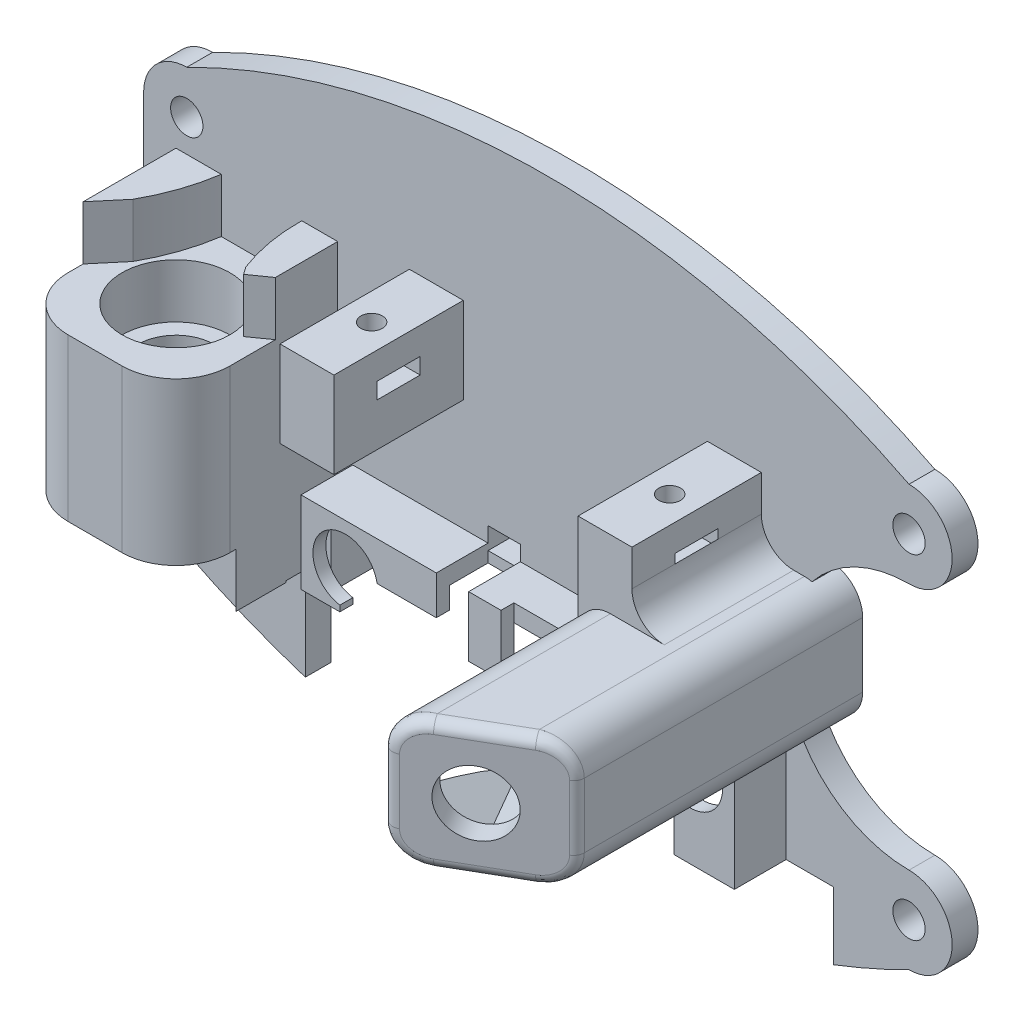
SolidWorks part; units mm, degrees
material "ABS"
ref_plane "Alzado" through (0, 0, 0) normal (0, 0, 1) x (1, 0, 0)
ref_plane "Planta" through (0, 0, 0) normal (0, 1, 0) x (1, 0, 0)
ref_plane "Vista lateral" through (0, 0, 0) normal (1, 0, 0) x (0, 0, -1)
sketch "Croquis1" plane through (0, 0, 0) normal (0, 0, 1) x (1, 0, 0)
  line L0 (-65.9407, 48.6885) -> (-65.9407, 17.6885)
  line L1 (-61.9407, 52.6885) -> (5.0593, 52.6885) construction
  line L2 (-61.9407, 13.6885) -> (5.0593, 13.6885) construction
  line L3 (-28.4407, 52.6885) -> (-28.4407, 60.6885) construction
  line L4 (-28.4407, 13.6885) -> (-28.4407, 5.6885) construction
  circle A0 centre (-61.9407, 48.6885) radius 1.5
  circle A1 centre (5.0593, 48.6885) radius 1.5
  circle A2 centre (5.0593, 17.6885) radius 1.5
  circle A3 centre (-61.9407, 17.6885) radius 1.5
  arc A4 (-61.9407, 52.6885) -> (-65.9407, 48.6885) centre (-61.9407, 48.6885) ccw
  arc A5 (-65.9407, 17.6885) -> (-61.9407, 13.6885) centre (-61.9407, 17.6885) ccw
  arc A6 (-61.9407, 13.6885) -> (5.0593, 13.6885) centre (-28.4407, 79.8291) ccw
  arc A7 (5.0593, 13.6885) -> (5.0593, 21.6885) centre (5.0593, 17.6885) ccw
  arc A8 (5.0593, 44.6885) -> (5.0593, 21.6885) centre (5.0593, 33.1885) ccw
  arc A9 (5.0593, 44.6885) -> (5.0593, 52.6885) centre (5.0593, 48.6885) ccw
  arc A10 (5.0593, 52.6885) -> (-61.9407, 52.6885) centre (-28.4407, -13.4521) ccw
  dimension "D2" = 8
  dimension "D3" = 8
  dimension "D5" = 4
  dimension "D6" = 4
  dimension "D7" = 3
  dimension "D8" = 3
  dimension "D9" = 4
  dimension "D10" = 3
  dimension "D11" = 4
  dimension "D12" = 3
  dimension "D13" = 11.5
  dimension "D1" = 67
  dimension "D4" = 31
extrude "Saliente-Extruir1" add sketch "Croquis1" along normal blind 2.4
sketch "Croquis3" plane through (0, 0, 2.4) normal (0, 0, 1) x (1, 0, 0)
  line L1 (-36.2907, 53.2855) -> (-13.6407, 53.2855)
  line L2 (-36.2907, 53.2855) -> (-36.2907, 49.2855)
  line L3 (-36.2907, 31.0355) -> (-13.6407, 31.0355)
  line L4 (-13.6407, 53.2855) -> (-13.6407, 49.2855)
  line L8 (-51.8407, 27.8355) -> (-51.8407, 7.4355) construction
  line L9 (-50.6407, 26.6355) -> (-13.6407, 26.6355) construction
  line L10 (-50.6407, 26.6355) -> (-50.6407, 8.6355) construction
  line L11 (-50.6407, 8.6355) -> (-13.6407, 8.6355) construction
  line L12 (-13.6407, 26.6355) -> (-13.6407, 8.6355) construction
  line L13 (-51.8407, 7.4355) -> (-12.4407, 7.4355) construction
  line L14 (-12.4407, 27.8355) -> (-12.4407, 7.4355) construction
  line L15 (-51.8407, 27.8355) -> (-12.4407, 27.8355) construction
  line L16 (-6.4407, 33.1885) -> (-12.4407, 33.1885) construction
  line L17 (-13.6407, 49.2855) -> (-8.6407, 49.2855)
  line L18 (-8.6407, 49.2855) -> (-8.6407, 46.7855)
  line L19 (-8.6407, 46.7855) -> (-13.6407, 46.7855)
  line L20 (-13.6407, 46.7855) -> (-13.6407, 31.0355)
  line L21 (-24.9657, 31.0355) -> (-24.9657, 53.2855) construction
  line L22 (-36.2907, 49.2855) -> (-41.2907, 49.2855)
  line L23 (-41.2907, 49.2855) -> (-41.2907, 46.7855)
  line L24 (-41.2907, 46.7855) -> (-36.2907, 46.7855)
  line L25 (-36.2907, 46.7855) -> (-36.2907, 31.0355)
  arc A0 (5.0593, 44.6885) -> (5.0593, 21.6885) centre (5.0593, 33.1885) ccw construction
  arc A1 (-61.9407, 13.6885) -> (5.0593, 13.6885) centre (-28.4407, 79.8291) ccw construction
  point P31 (-9.4407, 33.1885)
  dimension "D1" = 22.65
  dimension "D2" = 22.25
  dimension "D4" = 18
  dimension "D5" = 37
  dimension "D7" = 6
  dimension "D8" = 5
  dimension "D3" = 4
  dimension "D9" = 2.5
  dimension "D10" = 2.153
  dimension "D6" = 1.2
sketch "Croquis8" plane through (0, 0, 2.4) normal (0, 0, 1) x (1, 0, 0)
  line L0 (-6.4407, 33.1885) -> (-65.9407, 33.1885) construction
  line L1 (-65.9407, 48.6885) -> (-65.9407, 17.6885) construction
  line L3 (-62.9407, 40.6885) -> (-47.9407, 40.6885)
  line L4 (-62.9407, 40.6885) -> (-62.9407, 25.6885)
  line L5 (-62.9407, 25.6885) -> (-47.9407, 25.6885)
  line L6 (-47.9407, 40.6885) -> (-47.9407, 25.6885)
  arc A0 (5.0593, 44.6885) -> (5.0593, 21.6885) centre (5.0593, 33.1885) ccw construction
  point P11 (-47.9407, 33.1885)
  dimension "D1" = 15
  dimension "D2" = 15
  dimension "D3" = 3
extrude "Saliente-Extruir5" add sketch "Croquis8" along normal blind 15
sketch "Croquis10" plane through (0, 25.6885, 0) normal (0, -1, 0) x (1, 0, 0)
  line L0 (-62.9407, 2.4) -> (-47.9407, 2.4) construction
  line L1 (-62.9407, 17.4) -> (-47.9407, 17.4) construction
  circle A0 centre (-55.4407, 9.9) radius 5
  point P7 (-55.4407, 17.4)
  dimension "D1" = 10
  dimension "D2" = 7.5
extrude "Cortar-Extruir2" cut sketch "Croquis10" against normal blind 5
extrude "Cortar-Extruir3" cut sketch "Croquis10<2>" along normal blind 5 from surface starting at face at (-55.4407, 40.6885, 9.9)
sketch "Croquis10<2>" plane through (0, 25.6885, 0) normal (0, -1, 0) x (1, 0, 0) same geometry as "Croquis10"
sketch "Croquis11" plane through (0, 30.6885, 0) normal (0, -1, 0) x (1, 0, 0)
  circle A0 centre (-55.4407, 9.9) radius 3.5
  dimension "D1" = 7
extrude "Cortar-Extruir4" cut sketch "Croquis11" against normal up to surface (5 mm away) up to face at (-50.4407, 35.6885, 9.9)
fillet "Redondeo1" radius 5 2 edges at (-47.9407, 33.1885, 17.4) (-62.9407, 33.1885, 17.4)
sketch "Croquis14" plane through (0, 0, 2.4) normal (0, 0, 1) x (1, 0, 0)
  line L1 (-44.9407, 26.8355) -> (-7.9407, 26.8355)
  line L2 (-44.9407, 26.8355) -> (-44.9407, 1.8355)
  line L3 (-44.9407, 1.8355) -> (-7.9407, 1.8355)
  line L4 (-7.9407, 26.8355) -> (-7.9407, 1.8355)
  line L5 (-47.9407, 25.6885) -> (-47.9407, 40.6885) construction
  line L6 (-24.9657, 29.8355) -> (-24.9657, 26.8355) construction
  line L7 (-33.9907, 29.8355) -> (-30.9907, 29.8355)
  line L8 (-33.9907, 29.8355) -> (-33.9907, 27.8355)
  line L9 (-33.9907, 27.8355) -> (-30.9907, 27.8355)
  line L10 (-30.9907, 29.8355) -> (-30.9907, 27.8355)
  line L11 (-47.9407, 40.6885) -> (-62.9407, 40.6885) construction
  dimension "D1" = 37
  dimension "D2" = 25
  dimension "D3" = 1
  dimension "D4" = 3
  dimension "D5" = 2
  dimension "D6" = 3
  dimension "D7" = 13.95
  dimension "D8" = 13.853
extrude "Cortar-Extruir7" cut sketch "Croquis14" against normal up to next
sketch "Croquis15" plane through (0, 0, 2.4) normal (0, 0, 1) x (1, 0, 0)
  line L0 (-44.9407, 7.5479) -> (-44.9407, 26.8355)
  line L1 (-44.9407, 26.8355) -> (-33.9907, 26.8355)
  line L2 (-7.9407, 26.8355) -> (-7.9407, 8.579)
  line L3 (-46.5407, 7.9318) -> (-46.5407, 28.4355)
  line L4 (-46.5407, 28.4355) -> (-33.9907, 28.4355)
  line L5 (-33.9907, 29.8355) -> (-33.9907, 27.8355) construction
  line L6 (-33.9907, 28.4355) -> (-33.9907, 26.8355)
  line L7 (-30.9907, 28.4355) -> (-30.9907, 26.8355)
  line L8 (-30.9907, 27.8355) -> (-30.9907, 29.8355) construction
  line L9 (-30.9907, 26.8355) -> (-7.9407, 26.8355)
  line L10 (-30.9907, 28.4355) -> (-6.3407, 28.4355)
  line L11 (-6.3407, 28.4355) -> (-6.3407, 9.0589)
  arc A0 (-61.9407, 13.6885) -> (-44.9407, 7.5479) centre (-28.4407, 79.8291) ccw construction
  arc A1 (-7.9407, 8.579) -> (5.0593, 13.6885) centre (-28.4407, 79.8291) ccw construction
  arc A9 (-61.9407, 13.6885) -> (-44.9407, 7.5479) centre (-28.4407, 79.8291) ccw
  arc A10 (-46.5407, 7.9318) -> (-44.9407, 7.5479) centre (-28.4407, 79.8291) ccw
  arc A12 (-7.9407, 8.579) -> (5.0593, 13.6885) centre (-28.4407, 79.8291) ccw
  arc A13 (-7.9407, 8.579) -> (-6.3407, 9.0589) centre (-28.4407, 79.8291) ccw
  dimension "D1" = 1.6
  dimension "D2" = 1.6
  dimension "D3" = 1.6
  dimension "D4" = 1.6
  dimension "D5" = 0
  dimension "D6" = 0
extrude "Saliente-Extruir6" add sketch "Croquis15" along normal blind 3.6
sketch "Croquis16" plane through (0, 0, 6) normal (0, 0, 1) x (1, 0, 0)
  line L0 (-33.9907, 28.4355) -> (-46.5407, 28.4355)
  line L3 (-46.5407, 28.4355) -> (-46.5407, 7.9318)
  line L4 (-30.9907, 28.4355) -> (-6.3407, 28.4355)
  line L5 (-6.3407, 28.4355) -> (-6.3407, 9.0589)
  line L11 (-42.9407, 24.8355) -> (-33.9907, 24.8355)
  line L12 (-42.9407, 7.5479) -> (-42.9407, 24.8355)
  line L13 (-42.9407, 24.8355) -> (-33.9907, 24.8355)
  line L14 (-42.9407, 7.1202) -> (-42.9407, 24.8355)
  line L16 (-33.9907, 28.4355) -> (-33.9907, 24.8355)
  line L17 (-30.9907, 28.4355) -> (-30.9907, 22.8355)
  line L18 (-11.9407, 22.8355) -> (-11.9407, 8.579)
  line L19 (-30.9907, 22.8355) -> (-11.9407, 22.8355)
  line L20 (-11.9407, 22.8355) -> (-11.9407, 7.5479)
  line L21 (-30.9907, 22.8355) -> (-11.9407, 22.8355)
  arc A0 (-46.5407, 7.9318) -> (-42.9407, 7.1202) centre (-28.4407, 79.8291) ccw
  arc A1 (-11.9407, 7.5479) -> (-6.3407, 9.0589) centre (-28.4407, 79.8291) ccw
  dimension "D1" = 2
  dimension "D2" = 4
extrude "Saliente-Extruir7" add sketch "Croquis16" along normal blind 1.2
sketch "Croquis20" plane through (0, 25.6885, 0) normal (0, -1, 0) x (1, 0, 0)
  line L0 (-62.9407, 2.4) -> (-62.9407, 11.012)
  line L1 (-62.9407, 12.4) -> (-62.9407, 2.4) construction
  line L2 (-62.9407, 11.012) -> (-60.8397, 8.5116)
  line L4 (-62.9407, 2.4) -> (-47.9407, 2.4) construction
  line L5 (-58.7388, 2.4) -> (-62.9407, 2.4)
  line L6 (-47.9407, 2.4) -> (-47.9407, 11.8496)
  line L7 (-47.9407, 12.4) -> (-47.9407, 2.4) construction
  line L10 (-51.275, 2.4) -> (-47.9407, 2.4)
  line L12 (-50.162, 8.702) -> (-47.9407, 11.8496)
  arc A1 (-58.7388, 2.4) -> (-60.8397, 8.5116) centre (-76.1554, -0.1704) ccw
  arc A3 (-50.162, 8.702) -> (-51.275, 2.4) centre (-34.3459, 2.6594) ccw
extrude "Saliente-Extruir8" add sketch "Croquis20" along normal blind 5
ref_plane "Plano1" through (0, 33.1885, 0) normal (0, -1, 0) x (-1, 0, 0)
mirror "Simetría1" about plane through (0, 33.1885, 0) normal (0, -1, 0) of "Saliente-Extruir8"
sketch "Croquis22" plane through (0, 45.6885, 0) normal (0, 1, 0) x (1, 0, 0)
  line L0 (-47.9407, -11.8496) -> (-49.6705, -9.3985)
  line L2 (-49.6705, -9.3985) -> (-47.9407, -8.1778)
  line L3 (-47.9407, -2.4) -> (-47.9407, -11.8496) construction
  line L4 (-47.9407, -8.1778) -> (-47.9407, -11.8496)
  line L5 (-47.9407, -11.8496) -> (-50.162, -8.702) construction
  dimension "D1" = 3
extrude "Cortar-Extruir8" cut sketch "Croquis22" against normal up to vertex (5 mm away) up to point (-47.9407, 40.6885, 12.4)
sketch "Croquis24" plane through (0, 0, 2.4) normal (0, 0, 1) x (1, 0, 0)
  line L0 (-24.9657, 31.0355) -> (-24.9657, 53.2855) construction
  line L1 (-13.6407, 46.7855) -> (-8.6407, 46.7855)
  line L2 (-13.6407, 46.7855) -> (-13.6407, 38.7855)
  line L3 (-13.6407, 38.7855) -> (-8.6407, 38.7855)
  line L4 (-8.6407, 46.7855) -> (-8.6407, 38.7855)
  line L5 (-36.2907, 53.2855) -> (-13.6407, 53.2855) construction
  line L6 (-41.2907, 46.7855) -> (-41.2907, 38.7855)
  line L7 (-36.2907, 38.7855) -> (-41.2907, 38.7855)
  line L8 (-36.2907, 46.7855) -> (-36.2907, 38.7855)
  line L9 (-36.2907, 46.7855) -> (-41.2907, 46.7855)
  dimension "D1" = 8
extrude "Saliente-Extruir10" add sketch "Croquis24" along normal blind 12
sketch "Croquis25" plane through (0, 46.7855, 0) normal (0, 1, 0) x (1, 0, 0)
  line L0 (-8.6407, -14.4) -> (-8.6407, -2.4) construction
  line L1 (-8.6407, -14.4) -> (-13.6407, -14.4) construction
  line L2 (-13.6407, -14.4) -> (-36.2907, -14.4) construction
  line L3 (-24.9657, -14.4) -> (-24.9657, -8.0084) construction
  circle A0 centre (-11.1407, -8.4) radius 1
  circle A1 centre (-38.7907, -8.4) radius 1
  point P5 (-8.6407, -8.4)
  point P9 (-11.1407, -14.4)
  dimension "D1" = 2
extrude "Cortar-Extruir9" cut sketch "Croquis25" against normal blind 7
sketch "Croquis26" plane through (0, 0, 2.4) normal (0, 0, 1) x (1, 0, 0)
  line L1 (-13.6407, 40.4355) -> (-13.6407, 28.4355)
  line L2 (-6.3407, 28.4355) -> (-30.9907, 28.4355) construction
  line L3 (-13.6407, 28.4355) -> (-1.6407, 28.4355)
  line L6 (-1.6407, 40.4355) -> (-1.6407, 28.4355)
  line L7 (-13.6407, 40.4355) -> (-1.6407, 40.4355)
  line L8 (-13.6407, 46.7855) -> (-13.6407, 38.7855) construction
  circle A2 centre (-7.6407, 34.4355) radius 5 construction
  point P5 (-7.6407, 28.4355)
  point P12 (-7.6407, 34.3658)
  point P13 (-1.6407, 34.4355)
  dimension "D1" = 12
  dimension "D2" = 12
extrude "Saliente-Extruir11" add sketch "Croquis26" along normal blind 24 and the other way up to vertex (2.4 mm away) other way up to point (5.0593, 21.6885, 0)
sketch "Croquis27" plane through (0, 28.4355, 0) normal (0, -1, 0) x (1, 0, 0)
  line L0 (-1.6407, 26.4) -> (-13.6407, 26.4)
  line L1 (-13.6407, 26.4) -> (-13.6407, 33.3282)
  line L2 (-13.6407, 33.3282) -> (-1.6407, 26.4)
  dimension "D1" = 30
extrude "Saliente-Extruir12" add sketch "Croquis27" against normal up to surface (12 mm away) up to face at (-6.948, 40.4355, 10.8)
sketch "Croquis28" plane through (11.0214, 0, 19.0896) normal (0.5, 0, 0.866) x (0.866, 0, -0.5)
  line L1 (-28.4773, 34.4355) -> (-21.5491, 34.4355) construction
  line L2 (-28.4773, 40.4355) -> (-28.4773, 28.4355) construction
  line L3 (-21.5491, 34.4355) -> (-21.5491, 28.4355) construction
  line L4 (-14.6209, 28.4355) -> (-28.4773, 28.4355) construction
  circle A0 centre (-21.5491, 34.4355) radius 3
  point P6 (0, 0)
  dimension "D1" = 6
extrude "Cortar-Extruir10" cut sketch "Croquis28" against normal blind 2
sketch "Croquis29" plane through (10.0214, 0, 17.3575) normal (0.5, 0, 0.866) x (0.866, 0, -0.5)
  line L1 (-21.5491, 39.1698) -> (-25.6491, 36.8027)
  line L2 (-25.6491, 36.8027) -> (-25.6491, 32.0684)
  line L3 (-25.6491, 32.0684) -> (-21.5491, 29.7013)
  line L4 (-21.5491, 29.7013) -> (-17.4491, 32.0684)
  line L5 (-17.4491, 32.0684) -> (-17.4491, 36.8027)
  line L6 (-17.4491, 36.8027) -> (-21.5491, 39.1698)
  circle A0 centre (-21.5491, 34.4355) radius 4.1 construction
  dimension "D1" = 8.2
extrude "Cortar-Extruir11" cut sketch "Croquis29" against normal blind 18
fillet "Redondeo3" radius 3 5 edges at (-1.6407, 28.4355, 13.2) (-13.6407, 28.4355, 20.2641) (-13.6407, 40.4355, 23.8641) (-8.6407, 40.4355, 8.4) (-1.6407, 40.4355, 13.2)
fillet "Redondeo4" radius 1 9 edges at (-1.6407, 34.4355, 26.4) (-2.5194, 29.3142, 26.9073) (-7.6407, 28.4355, 29.8641) (-12.762, 29.3142, 32.8209) (-13.6407, 34.4355, 33.3282) (-7.6407, 40.4355, 29.8641) (-6.3407, 28.4355, 4.8) (-2.5194, 39.5569, 26.9073) (-12.762, 39.5569, 32.8209)
sketch "Croquis30" plane through (0, 0, 0) normal (0, 0, -1) x (-1, 0, 0)
  line L1 (42.9407, 7.1202) -> (50.9407, 7.1202)
  line L2 (42.9407, 7.1202) -> (42.9407, 20.8355)
  line L3 (42.9407, 20.8355) -> (50.9407, 20.8355)
  line L4 (50.9407, 7.1202) -> (50.9407, 20.8355)
  line L5 (44.9407, 26.8355) -> (7.9407, 26.8355) construction
  line L7 (11.9407, 7.5479) -> (1.9407, 7.5479)
  line L8 (11.9407, 7.5479) -> (11.9407, 16.8355)
  line L9 (11.9407, 16.8355) -> (1.9407, 16.8355)
  line L10 (1.9407, 7.5479) -> (1.9407, 16.8355)
  line L11 (7.9407, 26.8355) -> (7.9407, 8.579) construction
  line L12 (44.9407, 7.5479) -> (44.9407, 26.8355) construction
  dimension "D1" = 6
  dimension "D2" = 10
  dimension "D3" = 6
  dimension "D4" = 6
extrude "Cortar-Extruir12" cut sketch "Croquis30" against normal up to vertex (7.2 mm away) up to point (-6.3407, 9.0589, 7.2)
sketch "Croquis31" plane through (-41.2907, 0, 0) normal (-1, 0, 0) x (0, 0, 1)
  line L0 (14.4, 46.7855) -> (2.4, 46.7855) construction
  line L1 (10.4, 44.2855) -> (6.4, 44.2855)
  line L2 (10.4, 44.2855) -> (10.4, 42.7855)
  line L3 (10.4, 42.7855) -> (6.4, 42.7855)
  line L4 (6.4, 44.2855) -> (6.4, 42.7855)
  point P6 (8.4, 44.2855)
  point P7 (8.4, 46.7855)
  dimension "D1" = 1.5
  dimension "D2" = 4
  dimension "D3" = 2.5
extrude "Cortar-Extruir13" cut sketch "Croquis31" against normal up to vertex (32.65 mm away) up to point (-8.6407, 46.7855, 14.4)
sketch "Croquis32" plane through (0, 0, 7.2) normal (0, 0, 1) x (1, 0, 0)
  line L0 (-30.9907, 22.8355) -> (-11.9407, 22.8355) construction
  line L1 (-27.9907, 22.8355) -> (-22.9907, 22.8355)
  line L2 (-27.9907, 22.8355) -> (-27.9907, 28.4355)
  line L3 (-27.9907, 28.4355) -> (-22.9907, 28.4355)
  line L4 (-22.9907, 22.8355) -> (-22.9907, 28.4355)
  line L5 (-13.6407, 28.4355) -> (-30.9907, 28.4355) construction
  line L6 (-30.9907, 28.4355) -> (-30.9907, 22.8355) construction
  line L7 (-46.5407, 20.8355) -> (-6.3407, 20.8355) construction
  line L8 (-6.3407, 16.8355) -> (-6.3407, 27.4355) construction
  line L9 (-26.4407, 20.8355) -> (-26.4407, 11.4237) construction
  circle A0 centre (-10.4407, 24.3355) radius 3
  circle A1 centre (-42.4407, 24.3355) radius 3
  dimension "D5" = 6
  dimension "D1" = 3
  dimension "D2" = 5
  dimension "D3" = 2.5
  dimension "D4" = 2.5
extrude "Cortar-Extruir14" cut sketch "Croquis32" against normal up to vertex (1.2 mm away) up to point (-33.9907, 24.8355, 6)
